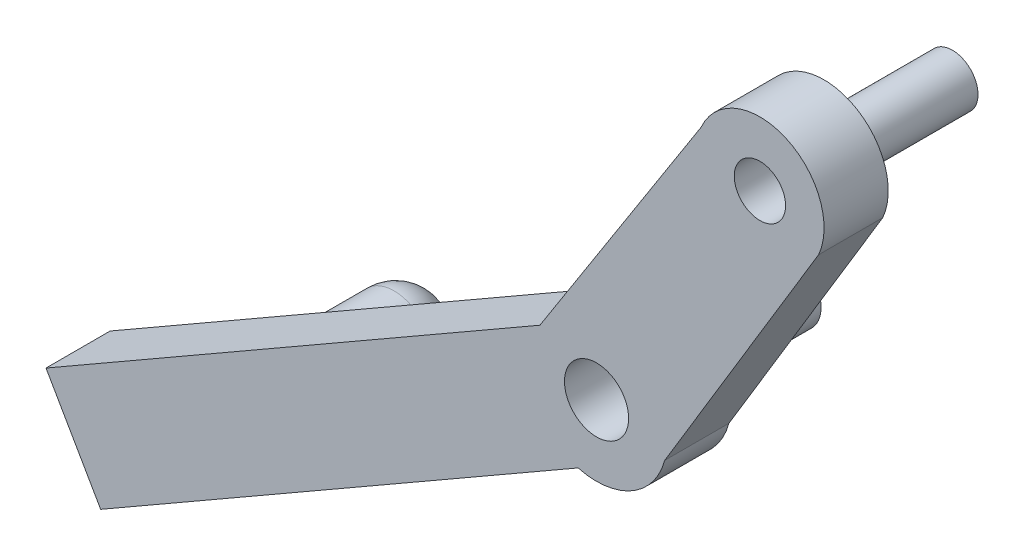
SolidWorks part; units mm, degrees
ref_plane "Front Plane" through (0, 0, 0) normal (0, 0, 1) x (1, 0, 0)
ref_plane "Top Plane" through (0, 0, 0) normal (0, 1, 0) x (1, 0, 0)
ref_plane "Right Plane" through (0, 0, 0) normal (1, 0, 0) x (0, 0, -1)
sketch "Sketch1" plane through (0, 0, 0) normal (0, 0, 1) x (0.4985, -0.8669, 0)
  line L0 (4.6263, -46.838) -> (4.6263, -41.838) construction
  line L2 (8.8991, 3.8691) -> (-2.3564, 24.18)
  line L3 (1.121, -3.909) -> (-10.421, 18.2671)
  line L4 (-2.3564, 24.18) -> (-10.421, 18.2671) construction
  line L6 (0.3536, -46.838) -> (8.8991, -46.838)
  line L7 (0.3536, -46.838) -> (0.3536, -2.4346)
  line L9 (8.8991, -46.838) -> (8.8991, -3.909)
  circle A0 centre (5.01, -0.02) radius 2.5
  arc A1 (1.121, -3.909) -> (8.8991, 3.8691) centre (5.01, -0.02) ccw
  arc A2 (-2.3564, 24.18) -> (-10.421, 18.2671) centre (-6.3887, 21.2235) ccw
  circle A3 centre (-6.3887, 21.2235) radius 2
  circle A5 centre (5.01, -0.02) radius 5.5 construction
  point P16 (10.01, -0.02)
  dimension "D2" = 4
  dimension "D3" = 5
  dimension "D5" = 5
  dimension "D4" = 25
  dimension "D6" = 42.929
  dimension "D7" = 8.5456
  dimension "D8" = 10
  dimension "D1" = 3
extrude "Boss-Extrude1" add sketch "Sketch1" along normal blind 5 contours L2 A2 L3 A1 A3 A0 | A1 L3 L7 L6 L9 region at (8.7385, 5.6702, 0) region at (-20.1011, -16.8788, 0)
sketch "Sketch8" plane through (0, 0, 0) normal (0, 0, -1) x (-1, 0, 0)
  line L0 (38.2963, -27.3606) -> (25.2932, -19.8826) construction
  line L1 (23.2692, -23.6476) -> (36.1662, -31.0645) construction
  line L2 (25.3993, -19.9436) -> (23.2692, -23.6476) construction
  line L3 (38.2963, -27.3606) -> (36.1662, -31.0645) construction
  circle A0 centre (25.2932, -19.8826) radius 3
  dimension "D1" = 6
  dimension "D3" = 4.2728
  dimension "D2" = 15
  dimension "D4" = 14.8776
extrude "Boss-Extrude3" add sketch "Sketch8" along normal blind 10
ref_plane "Plane1" through (2.3064, -4.0104, 0) normal (0.4985, -0.8669, 0) x (-0.8669, -0.4985, 0)
sketch "Sketch9" plane through (2.3064, -4.0104, 0) normal (0.4985, -0.8669, 0) x (-0.8669, -0.4985, 0)
  line L0 (31.838, 10) -> (31.838, 7) construction
  line L1 (34.838, 10) -> (28.838, 10) construction
  line L2 (31.838, 7) -> (34.838, 7) construction
  line L3 (31.838, 10) -> (32.838, 10) construction
  line L4 (32.838, 10) -> (34.838, 10)
  line L5 (34.838, 10) -> (34.838, 7)
  line L6 (34.838, 7.6139) -> (31.838, 7.6139) construction
  arc A0 (34.838, 7) -> (32.838, 10) centre (31.588, 7) ccw
  dimension "D3" = 3
  dimension "D1" = 2
  dimension "D2" = 3
revolve "Cut-Revolve1" cut sketch "Sketch9" angle 360 about L0
sketch "Sketch3" plane through (0, 0, 0) normal (0, 0, -1) x (-1, 0, 0)
  line L0 (36.092, -21.164) -> (18.7546, -11.1934) construction
  line L1 (36.1662, -31.0645) -> (40.4264, -23.6566) construction
  line L2 (40.4264, -23.6566) -> (18.7546, -11.1934) construction
  line L3 (40.4264, -23.6566) -> (1.9342, -1.5202) construction
  line L4 (18.7546, -11.1934) -> (14.4943, -18.6013) construction
  line L5 (36.1662, -31.0645) -> (-1.0478, -9.6632) construction
  line L6 (14.4943, -18.6013) -> (36.1662, -31.0645) construction
  line L7 (36.1662, -31.0645) -> (40.4264, -23.6566)
  line L8 (36.1662, -31.0645) -> (31.8318, -28.5719)
  line L9 (40.4264, -23.6566) -> (36.092, -21.164)
  line L10 (31.8318, -28.5719) -> (36.092, -21.164)
  line L11 (14.4943, -18.6013) -> (18.7546, -11.1934)
  line L12 (14.4943, -18.6013) -> (10.16, -16.1087)
  line L13 (18.7546, -11.1934) -> (14.4202, -8.7007)
  line L14 (10.16, -16.1087) -> (14.4202, -8.7007)
  dimension "D1" = 20
  dimension "D2" = 5
  dimension "D3" = 5
sketch "Sketch10" plane through (0, 0, 0) normal (0, 0, -1) x (-1, 0, 0)
  circle A0 centre (-15.2132, 16.1188) radius 2
  circle A1 centre (-2.4803, -4.353) radius 2.5
extrude "Boss-Extrude4" add sketch "Sketch10" along normal blind 10 separate body
move or copy body "Body-Move/Copy1" [suppressed] bodies to move or copy 105 106 107
